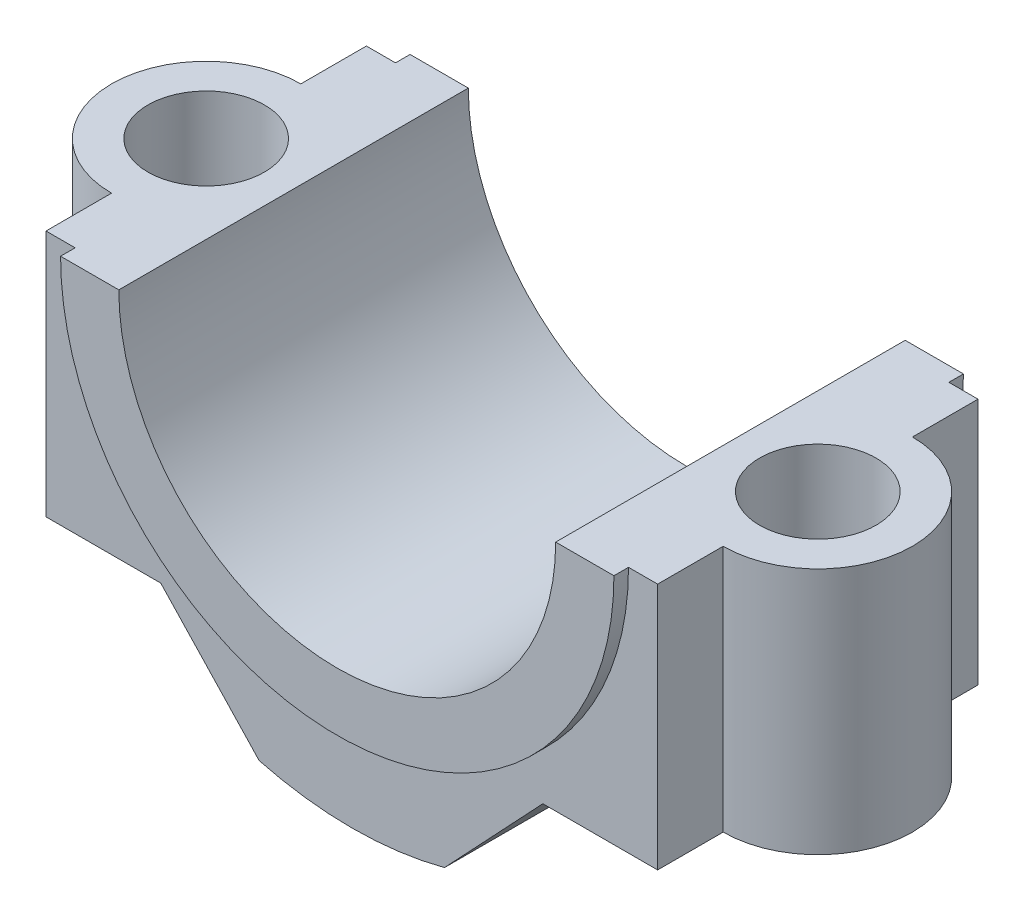
SolidWorks part; units mm, degrees
material "Сталь"
ref_plane "Спереди" through (0, 0, 0) normal (0, 0, 1) x (1, 0, 0)
ref_plane "Сверху" through (0, 0, 0) normal (0, 1, 0) x (1, 0, 0)
ref_plane "Справа" through (0, 0, 0) normal (1, 0, 0) x (0, 0, -1)
sketch "Эскиз3" plane through (0, 0, 0) normal (0, 0, 1) x (1, 0, 0)
  line L0 (-27.5, 95) -> (27.5, 95)
  line L1 (-27.5, 80) -> (27.5, 80)
  line L2 (-27.5, 80) -> (-27.5, 110)
  line L3 (-27.5, 110) -> (27.5, 110)
  line L4 (27.5, 80) -> (27.5, 110)
  line L5 (-27.5, 80) -> (27.5, 110) construction
  line L6 (-27.5, 110) -> (27.5, 80) construction
  line L8 (-15, 70) -> (15, 70)
  line L9 (-15, 70) -> (-15, 80)
  line L10 (-15, 80) -> (15, 80)
  line L11 (15, 70) -> (15, 80)
  line L12 (-15, 70) -> (15, 80) construction
  line L13 (-15, 80) -> (15, 70) construction
  circle A0 centre (0, 95) radius 15
  circle A1 centre (0, 95) radius 25
  point P10 (0, 75)
  dimension "D1" = 30
  dimension "D3" = 50
  dimension "D2" = 95
  dimension "D4" = 55
  dimension "D5" = 30
  dimension "D6" = 30
extrude "Бобышка-Вытянуть2" add sketch "Эскиз3" along normal blind 11 and the other way blind 11 separate body contours L9 A1 L11 L1 A0 | L0 A1 L1 A0 | A1 L0 L2 L1 | L1 A1 L0 A0 | A1 L1 L4 L0 region at (17.2039, 86.876, 0) region at (25.191, 86.0093, 0) region at (-17.2039, 86.876, 0) region at (0, 75.6692, 0) region at (-25.191, 86.0093, 0)
sketch "Эскиз5" plane through (0, 0, 11) normal (0, 0, 1) x (1, 0, 0)
  line L0 (15, 95) -> (27.5, 95) construction
  line L1 (-27.5, 95) -> (-15, 95) construction
  line L2 (-19, 95) -> (-15, 95)
  line L3 (15, 95) -> (19, 95)
  arc A0 (-15, 95) -> (15, 95) centre (0, 95) ccw construction
  arc A1 (-15, 95) -> (15, 95) centre (0, 95) ccw
  arc A2 (19, 95) -> (-19, 95) centre (0, 95) cw
  dimension "D1" = 19
extrude "Бобышка-Вытянуть3" add sketch "Эскиз5" along normal blind 1 contours A2 L2 A1 L3
mirror "Зеркальное отражение1" about plane through (0, 0, 0) normal (0, 0, 1) of "Бобышка-Вытянуть3"
sketch "Эскиз9" plane through (0, 95, 0) normal (0, 1, 0) x (1, 0, 0)
  circle A0 centre (21, 0) radius 4
  circle A1 centre (-21, 0) radius 4
  dimension "D1" = 8
extrude "Вырез-Вытянуть5" cut sketch "Эскиз9" against normal through all
sketch "Эскиз10" plane through (0, 80, 0) normal (0, -1, 0) x (1, 0, 0)
  line L0 (27.5, -11) -> (27.5, 11) construction
  line L1 (21, 6.5) -> (21, 11)
  line L2 (15, 11) -> (27.5, 11) construction
  line L3 (21, 11) -> (27.5, 11)
  line L4 (27.5, 11) -> (27.5, -11)
  line L5 (27.5, -11) -> (21, -11)
  line L7 (15, -11) -> (27.5, -11) construction
  line L8 (21, -11) -> (21, -6.5)
  circle A0 centre (21, 0) radius 6.5
  line M2 (27.5, 11) -> (15, 11)
  line M4 (15, -11) -> (27.5, -11)
  line M5 (27.5, -11) -> (27.5, 11)
extrude "Вырез-Вытянуть6" cut sketch "Эскиз10" against normal through all contours A0 L8 M4 M5 | A0 L4 L1 M2 region at (24.6755, 80, 7.874) region at (24.6755, 80, -7.874)
mirror "Зеркальное отражение2" about plane through (0, 0, 0) normal (1, 0, 0) of "Вырез-Вытянуть6"
chamfer "Фаска1" distance 20 distance2 5 1 edges at (-15, 75, 0) first distance on face at (0, 72.5, 0)
chamfer "Фаска2" distance 5 distance2 20 1 edges at (15, 75, 0) first distance on face at (15, 77.5, 0)
sketch "Эскиз11" plane through (0, 80, 0) normal (0, -1, 0) x (1, 0, 0)
  line L0 (-15, 11) -> (15, 11)
  line L1 (-15, -11) -> (15, -11)
  line L5 (-21, 11) -> (-21, 6.5)
  line L6 (-21, -6.5) -> (-21, -11)
  line L7 (-21, -11) -> (-15, -11)
  line L8 (-15, -11) -> (-15, 11)
  line L9 (-15, 11) -> (-21, 11)
  line L10 (-21, 11) -> (-21, 6.5)
  line L11 (-21, -6.5) -> (-21, -11)
  line L12 (-21, -11) -> (-15, -11)
  line L13 (-15, -11) -> (-15, 11)
  line L14 (-15, 11) -> (-21, 11)
  line L15 (21, 6.5) -> (21, 11)
  line L16 (21, 11) -> (15, 11)
  line L17 (15, 11) -> (15, -11)
  line L18 (15, -11) -> (21, -11)
  line L19 (21, -11) -> (21, -6.5)
  line L20 (21, 6.5) -> (21, 11)
  line L21 (21, 11) -> (15, 11)
  line L22 (15, 11) -> (15, -11)
  line L23 (15, -11) -> (21, -11)
  line L24 (21, -11) -> (21, -6.5)
  circle A0 centre (21, 0) radius 4 construction
  arc A1 (-21, 6.5) -> (-21, -6.5) centre (-21, 0) ccw
  arc A2 (-21, 6.5) -> (-21, -6.5) centre (-21, 0) ccw
  arc A3 (21, -6.5) -> (21, 6.5) centre (21, 0) ccw
  arc A4 (21, -6.5) -> (21, 6.5) centre (21, 0) ccw
  circle A5 centre (21, 0) radius 4
  circle A6 centre (-21, 0) radius 4 construction
  circle A7 centre (-21, 0) radius 4
  line M13 (-21, 11) -> (-21, 6.5)
  arc M14 (-21, 6.5) -> (-21, -6.5) centre (-21, 0) ccw
  line M15 (-21, -6.5) -> (-21, -11)
  line M16 (-21, -11) -> (-15, -11)
  line M17 (-15, -11) -> (-15, 11)
  line M18 (-15, 11) -> (-21, 11)
  circle M19 centre (-21, 0) radius 4
  dimension "D1" = 0
  dimension "D2" = 0
extrude "Бобышка-Вытянуть5" add sketch "Эскиз11" along normal blind 2 contours M18 M13 M14 M15 M16 M17 M19 | L24 A4 L20 L21 L22 L23 A5 | L22 L0 L1 M17 region at (0, 80, 0) region at (-15.253, 80, 0) region at (18, 80, 10.747)
equation "\"0ю5\"=1"
